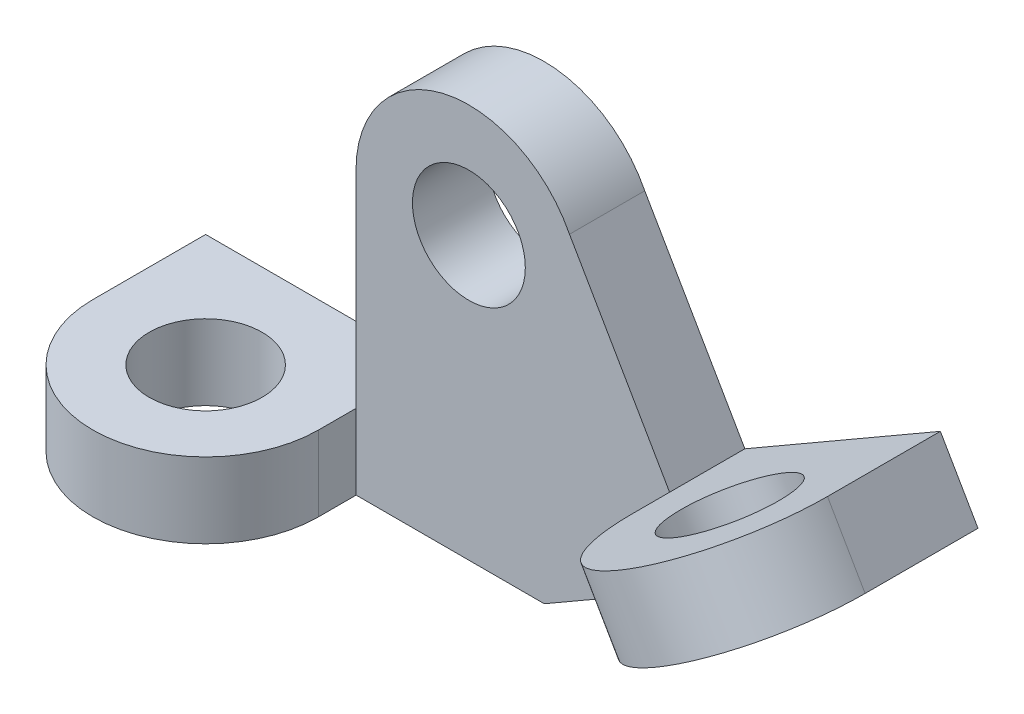
SolidWorks part; units mm, degrees
ref_plane "Front Plane" through (0, 0, 0) normal (0, 0, 1) x (1, 0, 0)
ref_plane "Top Plane" through (0, 0, 0) normal (0, 1, 0) x (1, 0, 0)
ref_plane "Right Plane" through (0, 0, 0) normal (1, 0, 0) x (0, 0, -1)
sketch "Sketch1" plane through (0, 0, 0) normal (0, 0, 1) x (1, 0, 0)
  line L0 (150, 0) -> (275, 0)
  line L1 (0, 0) -> (150, 0)
  line L2 (0, 0) -> (0, 50)
  line L3 (0, 50) -> (150, 50)
  line L4 (150, 0) -> (150, 50)
  line L5 (275, 0) -> (513.157, 137.5)
  line L6 (513.157, 137.5) -> (383.2532, 62.5)
  line L7 (513.157, 137.5) -> (488.157, 180.8013)
  line L8 (383.2532, 62.5) -> (358.2532, 105.8013)
  line L9 (488.157, 180.8013) -> (358.2532, 105.8013)
  line L10 (275, 0) -> (224.8935, 187) construction
  line L11 (358.2532, 105.8013) -> (291.7509, 220.9866)
  line L13 (150, 50) -> (149.8935, 187)
  circle A0 centre (224.8935, 187) radius 37.5
  arc A1 (291.7509, 220.9866) -> (149.8936, 186.8834) centre (224.8935, 187) ccw
  dimension "D10" = 75
  dimension "D11" = 150
  dimension "D1" = 50
  dimension "D2" = 150
  dimension "D3" = 275
  dimension "D4" = 275
  dimension "D5" = 150
  dimension "D6" = 50
  dimension "D7" = 150
  dimension "D8" = 187
  dimension "D9" = 75
extrude "Boss-Extrude2" add sketch "Sketch1" along normal blind 150 contours L1 L4 L3 L2 | L7 L9 L8 L5 region at (75, 25, 0) region at (435.7051, 121.6506, 0)
extrude "Boss-Extrude3" add sketch "Sketch1<4>" along normal blind 50 contours L11 A1 L13 L4 L0 A0 L5 L8 region at (245.1288, 111.4241, 0)
sketch "Sketch1<4>" plane through (0, 0, 0) normal (0, 0, 1) x (1, 0, 0) same geometry as "Sketch1"
fillet "Fillet2" 2 edges at (500.657, 159.1506, 150) (370.7532, 84.1506, 150) type full round first side face at (500.657, 159.1506, 75) second side face at (370.7532, 84.1506, 100) middle face at (435.7051, 121.6506, 150)
fillet "Fillet3" 2 edges at (0, 25, 150) (150, 25, 150) type full round first side face at (0, 25, 75) second side face at (150, 25, 100) middle face at (75, 25, 150)
sketch "Sketch2" plane through (0, 50, 0) normal (0, 1, 0) x (1, 0, 0)
  line L0 (0, -75) -> (150, -75) construction
  circle A0 centre (75, -75) radius 37.5
  dimension "D1" = 75
extrude "Cut-Extrude1" cut sketch "Sketch2" against normal through all
sketch "Sketch3" plane through (43.75, -75.7772, 0) normal (-0.5, 0.866, 0) x (0.866, 0.5, 0)
  line L0 (363.157, -75) -> (513.157, -75) construction
  circle A0 centre (438.157, -75) radius 37.5
  dimension "D1" = 75
extrude "Cut-Extrude2" cut sketch "Sketch3" against normal through all
